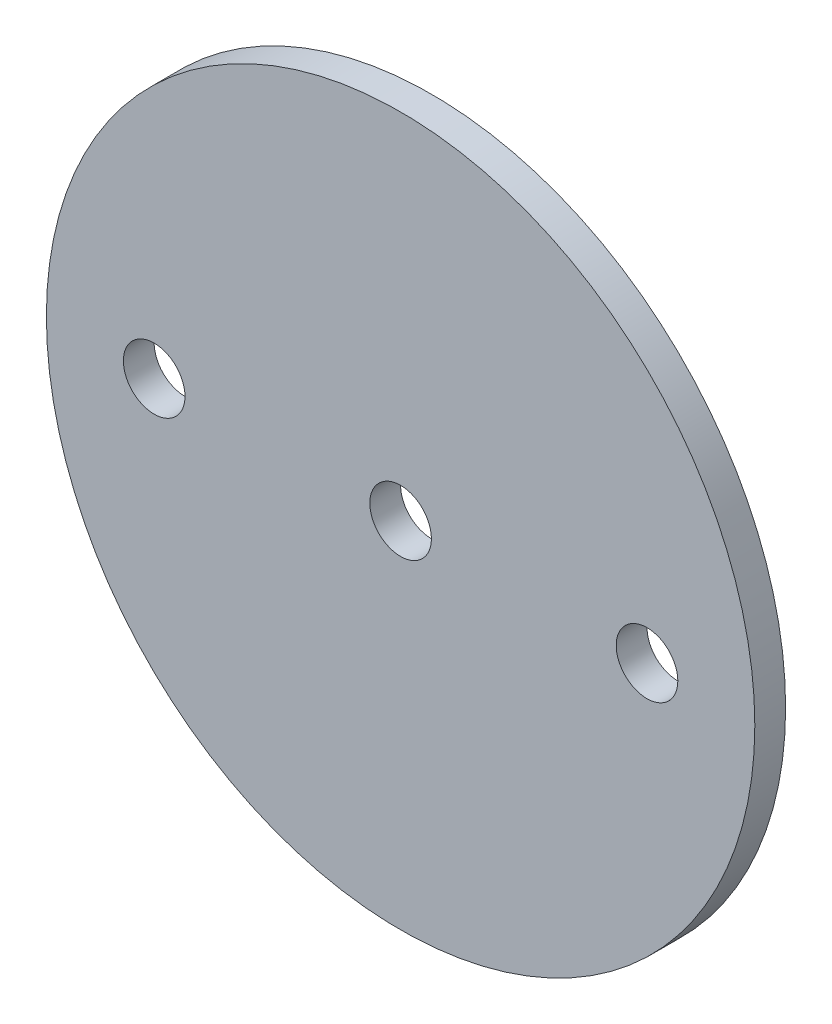
SolidWorks part; units mm, degrees
ref_plane "Front Plane" through (0, 0, 0) normal (0, 0, 1) x (1, 0, 0)
ref_plane "Top Plane" through (0, 0, 0) normal (0, 1, 0) x (1, 0, 0)
ref_plane "Right Plane" through (0, 0, 0) normal (1, 0, 0) x (0, 0, -1)
sketch "Sketch1" plane through (0, 0, 0) normal (0, 0, 1) x (1, 0, 0)
  circle A0 centre (0, 0) radius 36.5125
  dimension "D1" = 73.025
extrude "Boss-Extrude1" add sketch "Sketch1" along normal mid plane 3.175
sketch "Sketch2" plane through (0, 0, 1.5875) normal (0, 0, 1) x (1, 0, 0)
  line L0 (-1000, 0) -> (49000, 0) construction
  point P1 (0, 0)
  point P4 (25.4, 0)
  point P5 (-25.4, 0)
  dimension "D1" = 25.4
  dimension "D2" = 50.8
hole_wizard "1/4 (0.25) Diameter Hole1" positions "Sketch2" profile "Sketch3" hole size "1/4" standard "ANSI Inch" end condition through all
sketch "Sketch3" plane through (-25.4, 0, 1.5875) normal (1, 0, 0) x (0, -1, 0)
  line L0 (0, 0) -> (0, 3.175)
  line L1 (0, 3.175) -> (3.175, 3.175)
  line L2 (3.175, 3.175) -> (3.175, 0)
  line L5 (3.175, 0) -> (0, 0)
  line L11 (0, -6.35) -> (0, 107.95) construction
  dimension "Thru Hole Dia." = 6.35
  dimension "Thru Hole Depth" = 3.175
equation "\"AIRFRAME_OD\"= 3.091in"
equation "\"AIRFRAME_ID\"= 3.00in"
equation "\"FLAT_T\" = 0.125in"
equation "\"NOSE_EXP_L\"= 3.5in"
equation "\"NOSE_SHOULDER_L\" = 5in"
equation "\"MAIN_L\" = 30in"
equation "\"RECO_COUP_L\" = 6in"
equation "\"RECO_SWITCH_L\" = 1.5in"
equation "\"DROGUE_L\" = 14in"
equation "\"ATS_FORE_COUP_L\" = 4in"
equation "\"ATS_AFT_COUP_L\" = 4in"
equation "\"LOWER_L\" = 16in"
equation "\"FIN_N\" = 4"
equation "\"CR_AFT_X\" = 0.5in"
equation "\"CR_FORE_X\" = 6in"
equation "\"FIN_ROOT\" = 5in"
equation "\"FIN_X\" = 0.75in"
equation "\"MOTOR_OD\" = 2.25in"
equation "\"MOTOR_ID\" = 2.126in"
equation "\"COUPLER_OD\" = 2.998in"
equation "\"COUPLER_ID\" = 2.875in"
equation "\"D1@Sketch1\"=\"COUPLER_ID\""
equation "\"D1@Boss-Extrude1\"=\"FLAT_T\""
equation "\"RECO_ROD_X\" = 1.5in"
equation "\"ATS_ROD_X\" = 2in"
equation "\"D1@Sketch2\"=\"ATS_ROD_X\"*0.5"
equation "\"D2@Sketch2\"=\"ATS_ROD_X\""
